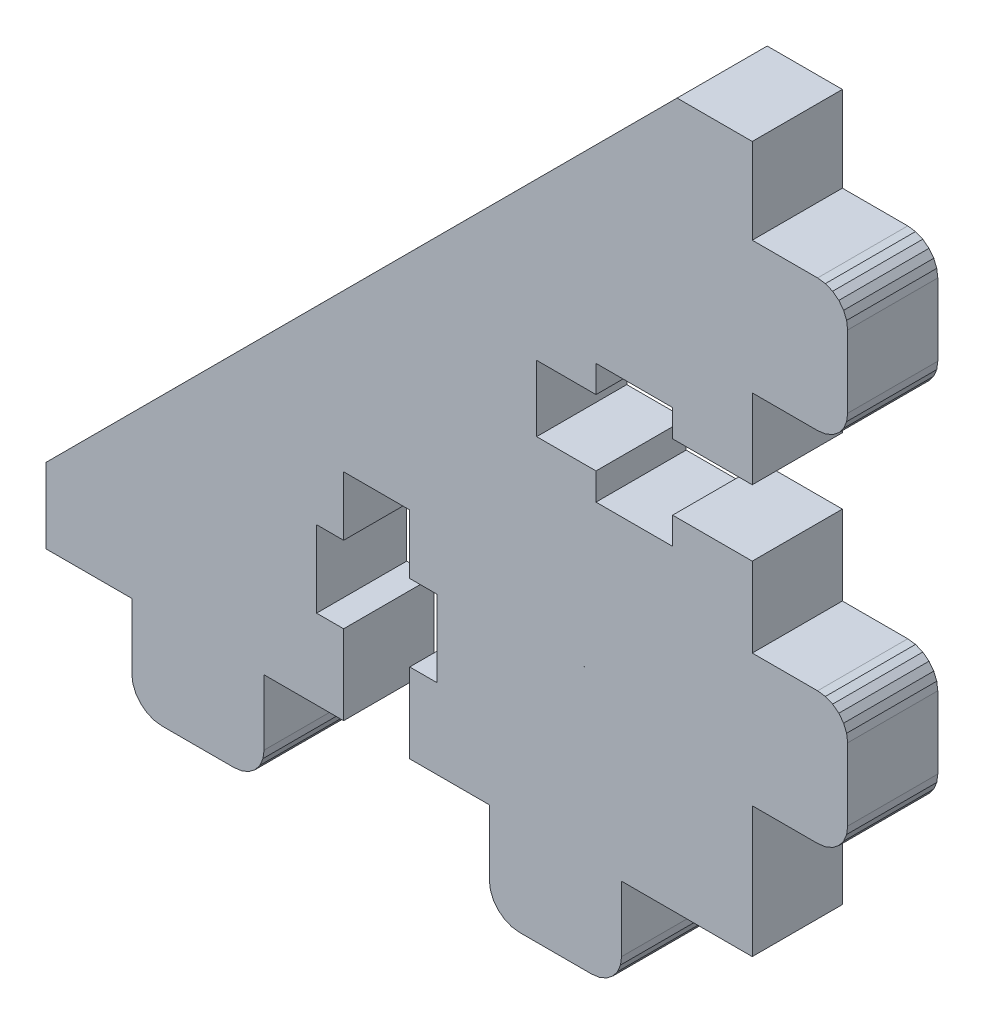
SolidWorks part; units mm, degrees
material "Maple"
ref_plane "Front Plane" through (0, 0, 0) normal (0, 0, 1) x (1, 0, 0)
ref_plane "Top Plane" through (0, 0, 0) normal (0, 1, 0) x (1, 0, 0)
ref_plane "Right Plane" through (0, 0, 0) normal (1, 0, 0) x (0, 0, -1)
sketch "Sketch1" plane through (0, 0, 0) normal (0, 0, 1) x (1, 0, 0)
  line L7938 (412.9021, 120.912) -> (418.0021, 120.912)
  line L7939 (412.9021, 119.112) -> (412.9021, 120.912)
  line L7940 (396.1021, 106.262) -> (400.5021, 106.262)
  line L7941 (400.5021, 106.262) -> (400.5021, 102.312)
  line L7942 (423.3021, 138.905) -> (418.2981, 138.905)
  line L7943 (396.1021, 97.212) -> (394.3021, 97.212)
  line L7944 (396.1021, 102.312) -> (396.1021, 106.262)
  line L7945 (408.9521, 114.712) -> (408.9521, 119.112)
  line L7946 (423.3021, 119.112) -> (423.3021, 124.412)
  line L7947 (376.305, 91.912) -> (376.305, 96.9133)
  line L7948 (412.9021, 114.712) -> (408.9521, 114.712)
  line L7949 (402.3021, 102.312) -> (402.3021, 97.212)
  line L7950 (405.8021, 91.912) -> (405.8021, 87.562)
  line L7951 (396.1021, 91.912) -> (396.1021, 97.212)
  line L7952 (400.5021, 97.212) -> (400.5021, 91.912)
  line L7953 (423.3021, 124.412) -> (427.6521, 124.412)
  line L7954 (418.0021, 114.712) -> (418.0021, 112.912)
  line L7955 (423.3021, 91.912) -> (414.6021, 91.912)
  line L7956 (418.0021, 119.112) -> (423.3021, 119.112)
  line L7957 (400.5021, 91.912) -> (405.8021, 91.912)
  line L7958 (423.3021, 100.612) -> (423.3021, 91.912)
  line L7959 (423.3021, 114.712) -> (418.0021, 114.712)
  line L7960 (412.9021, 112.912) -> (412.9021, 114.712)
  line L7961 (394.3021, 102.312) -> (396.1021, 102.312)
  line L7962 (400.5021, 102.312) -> (402.3021, 102.312)
  line L7963 (418.0021, 112.912) -> (412.9021, 112.912)
  line L7964 (390.8021, 91.912) -> (396.1021, 91.912)
  line L7965 (408.9521, 119.112) -> (412.9021, 119.112)
  line L7966 (418.0021, 120.912) -> (418.0021, 119.112)
  line L7967 (423.3021, 100.612) -> (427.6521, 100.612)
  line L7968 (382.0021, 91.912) -> (376.305, 91.912)
  line L7969 (402.3021, 97.212) -> (400.5021, 97.212)
  line L7970 (423.3021, 109.412) -> (423.3021, 114.712)
  line L7971 (382.0021, 91.912) -> (382.0021, 87.562)
  line L7972 (394.3021, 97.212) -> (394.3021, 102.312)
  line L7973 (384.0021, 85.562) -> (388.8021, 85.562)
  line L7974 (384.0021, 85.562) -> (383.4845, 85.6301)
  line L7975 (383.4845, 85.6301) -> (383.0021, 85.83)
  line L7976 (383.0021, 85.83) -> (382.5879, 86.1478)
  line L7977 (382.5879, 86.1478) -> (382.2701, 86.562)
  line L7978 (382.2701, 86.562) -> (382.0703, 87.0444)
  line L7979 (382.0703, 87.0444) -> (382.0021, 87.562)
  line L7980 (390.8021, 87.562) -> (390.8021, 91.912)
  line L7981 (390.8021, 87.562) -> (390.734, 87.0444)
  line L7982 (390.734, 87.0444) -> (390.5342, 86.562)
  line L7983 (390.5342, 86.562) -> (390.2163, 86.1478)
  line L7984 (390.2163, 86.1478) -> (389.8021, 85.83)
  line L7985 (389.8021, 85.83) -> (389.3198, 85.6301)
  line L7986 (389.3198, 85.6301) -> (388.8021, 85.562)
  line L7987 (412.6021, 85.562) -> (413.1197, 85.6301)
  line L7988 (413.1197, 85.6301) -> (413.6021, 85.83)
  line L7989 (413.6021, 85.83) -> (414.0163, 86.1478)
  line L7990 (414.0163, 86.1478) -> (414.3342, 86.562)
  line L7991 (414.3342, 86.562) -> (414.534, 87.0444)
  line L7992 (414.6021, 87.562) -> (414.6021, 91.912)
  line L7993 (414.534, 87.0444) -> (414.6021, 87.562)
  line L7994 (407.8021, 85.562) -> (412.6021, 85.562)
  line L7995 (407.8021, 85.562) -> (407.2845, 85.6301)
  line L7996 (407.2845, 85.6301) -> (406.8021, 85.83)
  line L7997 (406.8021, 85.83) -> (406.3879, 86.1478)
  line L7998 (406.3879, 86.1478) -> (406.0701, 86.562)
  line L7999 (406.0701, 86.562) -> (405.8703, 87.0444)
  line L8000 (405.8703, 87.0444) -> (405.8021, 87.562)
  line L8001 (429.6521, 126.412) -> (429.6521, 131.212)
  line L8002 (429.6521, 126.412) -> (429.584, 125.8944)
  line L8003 (429.584, 125.8944) -> (429.3842, 125.412)
  line L8004 (429.3842, 125.412) -> (429.0663, 124.9978)
  line L8005 (429.0663, 124.9978) -> (428.6521, 124.6799)
  line L8006 (428.6521, 124.6799) -> (428.1697, 124.4801)
  line L8007 (428.1697, 124.4801) -> (427.6521, 124.412)
  line L8008 (427.6521, 133.212) -> (423.3021, 133.212)
  line L8009 (427.6521, 133.212) -> (428.1697, 133.1438)
  line L8010 (428.1697, 133.1438) -> (428.6521, 132.944)
  line L8011 (428.6521, 132.944) -> (429.0663, 132.6262)
  line L8012 (429.0663, 132.6262) -> (429.3842, 132.212)
  line L8013 (429.3842, 132.212) -> (429.584, 131.7296)
  line L8014 (429.584, 131.7296) -> (429.6521, 131.212)
  line L8015 (429.6521, 102.612) -> (429.6521, 107.412)
  line L8016 (429.6521, 102.612) -> (429.584, 102.0944)
  line L8017 (429.584, 102.0944) -> (429.3842, 101.612)
  line L8018 (429.3842, 101.612) -> (429.0663, 101.1978)
  line L8019 (429.0663, 101.1978) -> (428.6521, 100.88)
  line L8020 (428.6521, 100.88) -> (428.1697, 100.6801)
  line L8021 (428.1697, 100.6801) -> (427.6521, 100.612)
  line L8022 (427.6521, 109.412) -> (423.3021, 109.412)
  line L8023 (427.6521, 109.412) -> (428.1697, 109.3438)
  line L8024 (428.1697, 109.3438) -> (428.6521, 109.144)
  line L8025 (428.6521, 109.144) -> (429.0663, 108.8262)
  line L8026 (429.0663, 108.8262) -> (429.3842, 108.412)
  line L8027 (429.3842, 108.412) -> (429.584, 107.9296)
  line L8028 (429.584, 107.9296) -> (429.6521, 107.412)
  line L8456 (423.3021, 133.212) -> (423.3021, 138.905)
  line L8457 (418.2981, 138.905) -> (376.305, 96.9133)
  line L9762 (411.7707, 100.8458) -> (411.7707, 105.1537)
  line L9763 (411.7707, 105.1537) -> (411.7707, 103.0308)
  line L9764 (411.7707, 103.0308) -> (414.0061, 103.0308)
  line L9765 (414.0061, 103.0308) -> (414.0061, 105.1537)
  line L9766 (414.0061, 105.1537) -> (414.0061, 100.8458)
  line L9767 (414.0061, 100.8458) -> (414.0061, 103.0312)
  line L9768 (414.0061, 103.0312) -> (411.7707, 103.0312)
  line L9769 (411.7707, 103.0312) -> (411.7707, 100.8458)
extrude "Boss-Extrude1" add sketch "Sketch1" along normal blind 6 contours L7942 L8457 L7947 L7968 L7971 L7979 L7978 L7977 L7976 L7975 L7974 L7973 L7986 L7985 L7984 L7983 L7982 L7981 L7980 L7964 L7951 L7943 L7972 L7961 L7944 L7940 L7941 L7962 L7949 L7969 L7952 L7957 L7950 L8000 L7999 L7998 L7997 L7996 L7995 L7994 L7987 L7988 L7989 L7990 L7991 L7993 L7992 L7955 L7958 L7967 L8021 region at (406.9724, 108.2407, 0)
